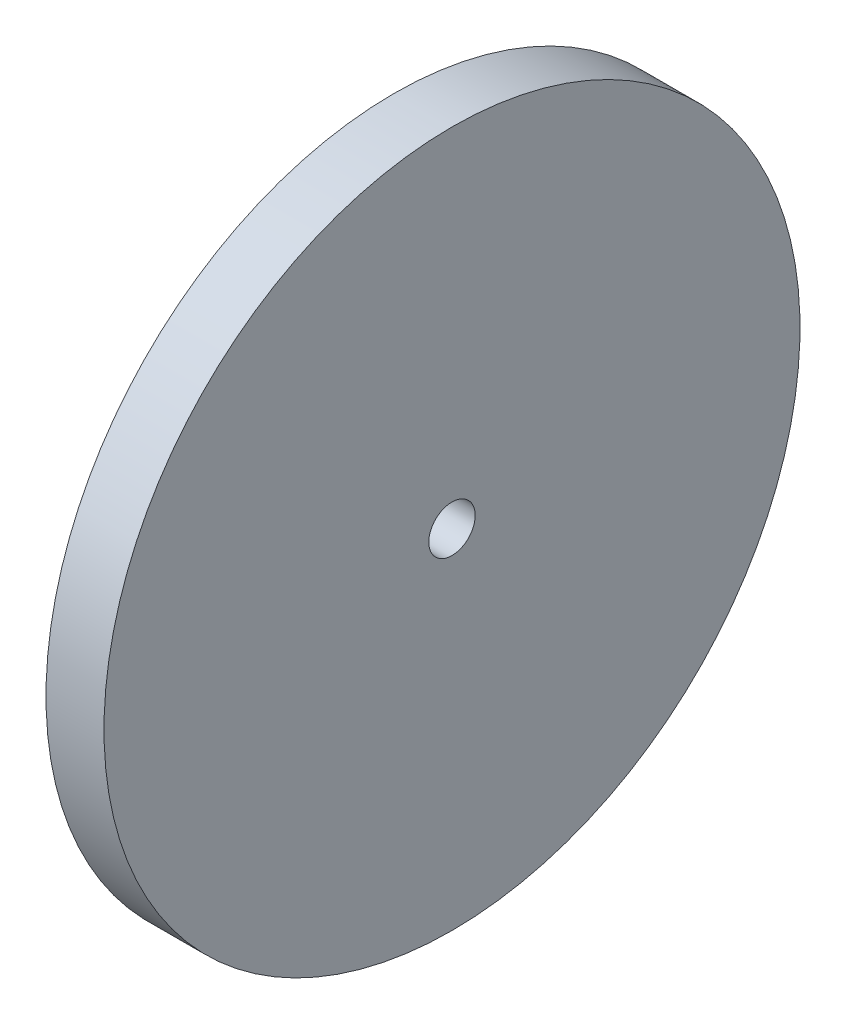
SolidWorks part; units mm, degrees
ref_plane "Front Plane" through (0, 0, 0) normal (0, 0, 1) x (1, 0, 0)
ref_plane "Top Plane" through (0, 0, 0) normal (0, 1, 0) x (1, 0, 0)
ref_plane "Right Plane" through (0, 0, 0) normal (1, 0, 0) x (0, 0, -1)
sketch "Sketch1" plane through (0, 0, 0) normal (0, 0, 1) x (1, 0, 0)
  line L0 (-12.5, 0) -> (12.5, 0)
  line L5 (-12.5, 15) -> (12.5, 15)
  line L10 (12.5, 15) -> (12.5, 0)
  line L14 (-12.5, 15) -> (-12.5, 0)
  arc A1 (-10, 15) -> (10, 15) centre (0, 15) ccw
  point P3 (0, 0)
  dimension "D3" = 10
  dimension "D1" = 15
  dimension "D2" = 25
revolve "Revolve1" add sketch "Sketch1" angle 360 about L0 region at (-12.2085, 7.5, 0)
sketch "Sketch2" plane through (12.5, 0, 0) normal (1, 0, 0) x (0, 0, -1)
  line L0 (0, 37.5) -> (0, -37.5) construction
  circle A1 centre (0, 0) radius 1
  dimension "D1" = 2
extrude "Cut-Extrude1" cut sketch "Sketch2" against normal through all
sketch "Sketch3" plane through (12.5, 0, 0) normal (1, 0, 0) x (0, 0, -1)
  circle A0 centre (0, 0) radius 15
  circle A1 centre (0, 0) radius 15 construction
extrude "Cut-Extrude2" cut sketch "Sketch3" against normal blind 22.5
